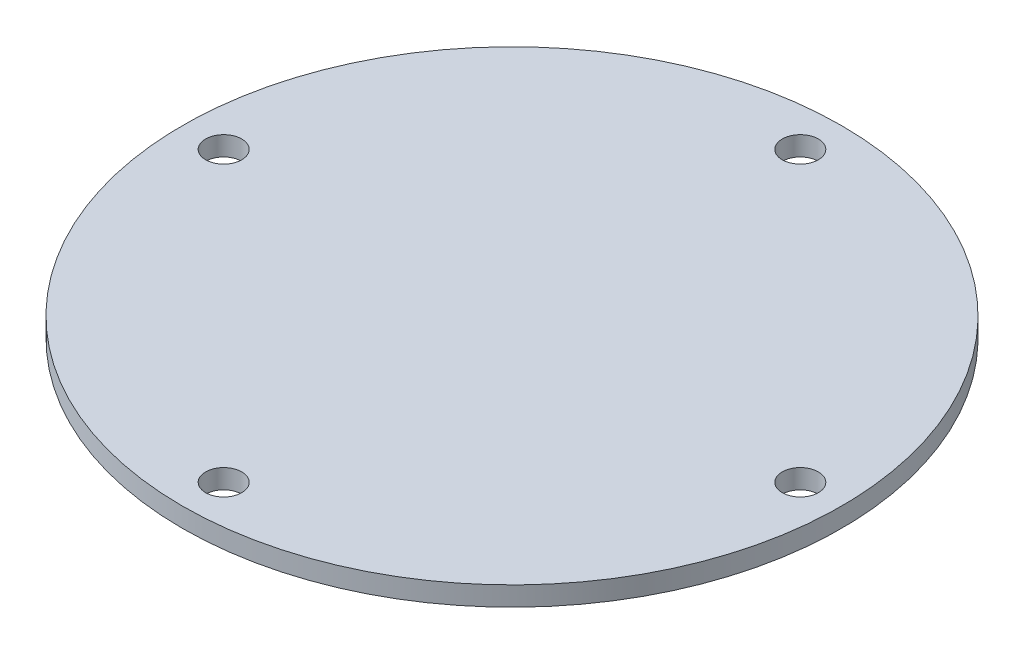
SolidWorks part; units mm, degrees
ref_plane "Front Plane" through (0, 0, 0) normal (0, 0, 1) x (1, 0, 0)
ref_plane "Top Plane" through (0, 0, 0) normal (0, 1, 0) x (1, 0, 0)
ref_plane "Right Plane" through (0, 0, 0) normal (1, 0, 0) x (0, 0, -1)
sketch "Sketch1" plane through (0, 0, 0) normal (0, 1, 0) x (1, 0, 0)
  circle A0 centre (0, 0) radius 63.9
  dimension "PCBdiam" = 127.8
extrude "Boss-Extrude1" add sketch "Sketch1" along normal blind 3.75
hole_wizard "M6 Clearance Hole1" positions "Sketch2" profile "Sketch4" hole size "M6" standard "ANSI Metric" end condition through all
sketch "Sketch2" plane through (0, 3.75, 0) normal (0, 1, 0) x (1, 0, 0)
  line L0 (0, 0) -> (0, 29.5662) construction
  circle A0 centre (0, 0) radius 63.9 construction
  point P7 (-55.9, 0)
  dimension "holeRadius" = 55.9
sketch "Sketch4" plane through (-55.9, 3.75, 0) normal (1, 0, 0) x (0, 0, 1)
  line L0 (0, 0) -> (0, 3.75)
  line L1 (0, 3.75) -> (3.5, 3.75)
  line L2 (3.5, 3.75) -> (3.5, 0)
  line L5 (3.5, 0) -> (0, 0)
  line L11 (0, -6.35) -> (0, 107.95) construction
  dimension "Thru Hole Dia." = 7
  dimension "Thru Hole Depth" = 3.75
pattern_circular "CirPattern1" count 4 over 360 about axis through (0, 3.75, 0) along (0, -1, 0) of "M6 Clearance Hole1"
